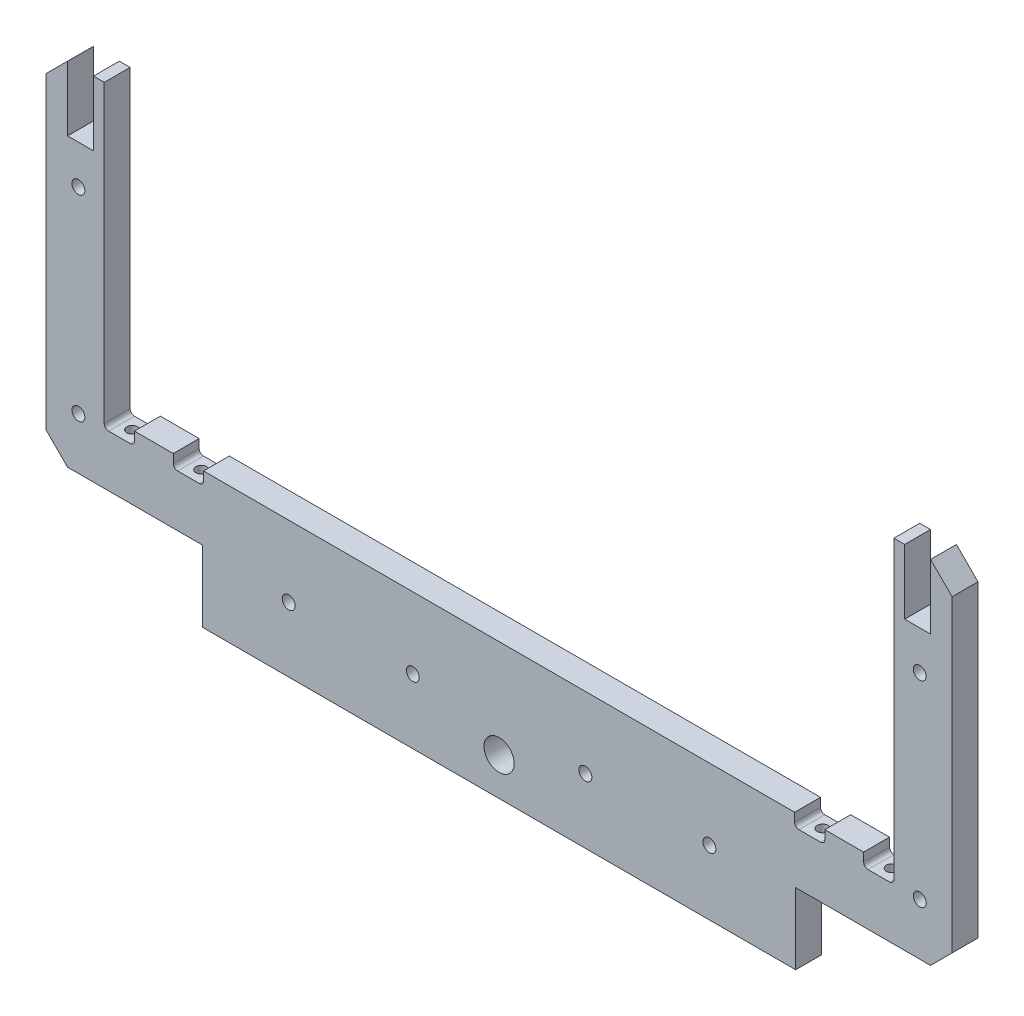
SolidWorks part; units mm, degrees
material "HDPE-green"
ref_plane "Front Plane" through (0, 0, 0) normal (0, 0, 1) x (1, 0, 0)
ref_plane "Top Plane" through (0, 0, 0) normal (0, 1, 0) x (1, 0, 0)
ref_plane "Right Plane" through (0, 0, 0) normal (1, 0, 0) x (0, 0, -1)
sketch "Sketch1" plane through (0, 0, 0) normal (0, 0, 1) x (1, 0, 0)
  line L1 (-137.5, -16.5) -> (137.5, -16.5)
  line L2 (-137.5, -16.5) -> (-137.5, 16.5)
  line L3 (-137.5, 16.5) -> (137.5, 16.5)
  line L4 (137.5, -16.5) -> (137.5, 16.5)
  line L5 (-137.5, -16.5) -> (137.5, 16.5) construction
  line L6 (-137.5, 16.5) -> (137.5, -16.5) construction
  point P0 (0, 0)
  dimension "D1" = 275
  dimension "D2" = 33
extrude "Boss-Extrude1" add sketch "Sketch1" along normal blind 12
sketch "Sketch2" plane through (0, 0, 12) normal (0, 0, 1) x (1, 0, 0)
  line L0 (137.5, 16.5) -> (-137.5, 16.5) construction
  line L1 (-16.5, 1) -> (20.0379, 1) construction
  circle A0 centre (0, 1) radius 7
  point P2 (0, 16.5)
  dimension "D1" = 15.5
  dimension "D2" = 14
extrude "Cut-Extrude1" cut sketch "Sketch2" against normal up to next
sketch "Sketch3" plane through (0, 0, 12) normal (0, 0, 1) x (1, 0, 0)
  line L1 (-210, 16.5) -> (210, 16.5)
  line L2 (-210, 16.5) -> (-210, 179.5)
  line L3 (-183, 46.5) -> (183, 46.5)
  line L4 (210, 16.5) -> (210, 179.5)
  line L5 (-210, 179.5) -> (-183, 179.5)
  line L8 (-183, 46.5) -> (-183, 179.5)
  line L9 (183, 179.5) -> (210, 179.5)
  line L13 (183, 46.5) -> (183, 179.5)
  circle A0 centre (0, 1) radius 7 construction
  dimension "D1" = 30
  dimension "D3" = 210
  dimension "D8" = 133
extrude "Boss-Extrude2" add sketch "Sketch3" against normal blind 12
sketch "Sketch4" plane through (0, 46.5, 0) normal (0, 1, 0) x (1, 0, 0)
  line L0 (-183, -6) -> (183, -6) construction
  line L1 (-183, 0) -> (-183, -12) construction
  line L2 (183, 0) -> (183, -12) construction
  line L4 (183, 0) -> (-183, 0) construction
  circle A0 centre (-144, -6) radius 2.5
  circle A1 centre (-176, -6) radius 2.5
  point P10 (0, 0)
  point P12 (0, 0)
  dimension "D1" = 5
  dimension "D2" = 5
  dimension "D3" = 144
  dimension "D4" = 176
extrude "Cut-Extrude2" cut sketch "Sketch4" against normal up to next
mirror "Mirror1" about plane through (0, 0, 0) normal (1, 0, 0) of "Cut-Extrude2"
sketch "Sketch5" plane through (0, 0, 12) normal (0, 0, 1) x (1, 0, 0)
  line L0 (-183, 46.5) -> (-183, 40.5)
  line L1 (-183, 40.5) -> (-169, 40.5)
  line L2 (-169, 40.5) -> (-169, 46.5)
  line L3 (183, 46.5) -> (-183, 46.5) construction
  line L4 (-169, 46.5) -> (-183, 46.5)
  line L5 (-151, 46.5) -> (-151, 40.5)
  line L6 (-151, 40.5) -> (-137, 40.5)
  line L7 (-137, 40.5) -> (-137, 46.5)
  line L8 (-151, 46.5) -> (-137, 46.5)
  circle A0 centre (0, 1) radius 7 construction
  dimension "D1" = 14
  dimension "D2" = 6
  dimension "D3" = 6
  dimension "D4" = 14
  dimension "D5" = 137
  dimension "D6" = 169
extrude "Cut-Extrude3" cut sketch "Sketch5" against normal up to next
fillet "Fillet1" radius 2 4 edges at (-137, 40.5, 6) (-151, 40.5, 6) (-169, 40.5, 6) (-183, 40.5, 6)
mirror "Mirror2" about plane through (0, 0, 0) normal (1, 0, 0) of "Fillet1", "Cut-Extrude3"
chamfer "Chamfer1" distance 10 angle 45 2 edges at (210, 16.5, 6) (-210, 16.5, 6)
sketch "Sketch6" plane through (0, 0, 12) normal (0, 0, 1) x (1, 0, 0)
  line L0 (-183, 179.5) -> (-210, 179.5) construction
  line L1 (-200, 179.5) -> (-188, 179.5)
  line L2 (-200, 179.5) -> (-200, 149.5)
  line L3 (-200, 149.5) -> (-188, 149.5)
  line L4 (-188, 179.5) -> (-188, 149.5)
  line L5 (-210, 179.5) -> (-210, 26.5) construction
  dimension "D1" = 12
  dimension "D2" = 10
  dimension "D3" = 30
extrude "Cut-Extrude4" cut sketch "Sketch6" against normal up to next
mirror "Mirror3" about plane through (0, 0, 0) normal (1, 0, 0) of "Cut-Extrude4"
chamfer "Chamfer2" distance 10 angle 45 2 edges at (210, 179.5, 6) (-210, 179.5, 6)
hole_wizard "Ø6.0 (6) Diameter Hole1" positions "Sketch8" profile "Sketch7" hole size "Ø6.0" standard "ISO" end condition up to next
sketch "Sketch8" plane through (0, 0, 12) normal (0, 0, 1) x (1, 0, 0)
  line L0 (-200, 16.5) -> (-137.5, 16.5) construction
  line L2 (-183, 42.5) -> (-183, 179.5) construction
  point P0 (-195, 40.5)
  point P9 (-195, 131.5)
  dimension "D1" = 24
  dimension "D2" = 12
  dimension "D3" = 115
sketch "Sketch7" plane through (-195, 40.5, 12) normal (1, 0, 0) x (0, -1, 0)
  line L0 (0, 0) -> (0, 12.0011)
  line L1 (0, 12.0011) -> (3, 12.0011)
  line L2 (3, 12.0011) -> (3, 0)
  line L5 (3, 0) -> (0, 0)
  line L11 (0, -6.35) -> (0, 107.95) construction
  dimension "Thru Hole Dia." = 6
  dimension "Thru Hole Depth" = 12.0011
mirror "Mirror4" about plane through (0, 0, 0) normal (1, 0, 0) of "Ø6.0 (6) Diameter Hole1"
hole_wizard "Ø6.0 (6) Diameter Hole2" positions "Sketch10" profile "Sketch9" hole size "Ø6.0" standard "ISO"
sketch "Sketch10" plane through (0, 0, 12) normal (0, 0, 1) x (1, 0, 0)
  line L0 (-137.5, -16.5) -> (137.5, -16.5) construction
  line L1 (-137.5, 16.5) -> (-137.5, -16.5) construction
  line L2 (137.5, -16.5) -> (137.5, 16.5) construction
  circle A0 centre (0, 1) radius 7 construction
  point P0 (-97.5, 13.5)
  point P1 (-40, 13.5)
  point P3 (40, 13.5)
  point P5 (97.5, 13.5)
  dimension "D1" = 30
  dimension "D2" = 30
  dimension "D3" = 30
  dimension "D4" = 30
  dimension "D5" = 40
  dimension "D6" = 40
  dimension "D7" = 40
  dimension "D8" = 40
sketch "Sketch9" plane through (-97.5, 13.5, 12) normal (1, 0, 0) x (0, -1, 0)
  line L0 (0, 0) -> (0, 13.8026)
  line L1 (0, 13.8026) -> (3, 12)
  line L2 (3, 12) -> (3, 0)
  line L5 (3, 0) -> (0, 0)
  line L10 (0, 13.8026) -> (-3, 12) construction
  line L11 (0, -6.35) -> (0, 107.95) construction
  dimension "Hole Dia." = 6
  dimension "Hole Depth" = 12
  dimension "Drill Angle" = 118
